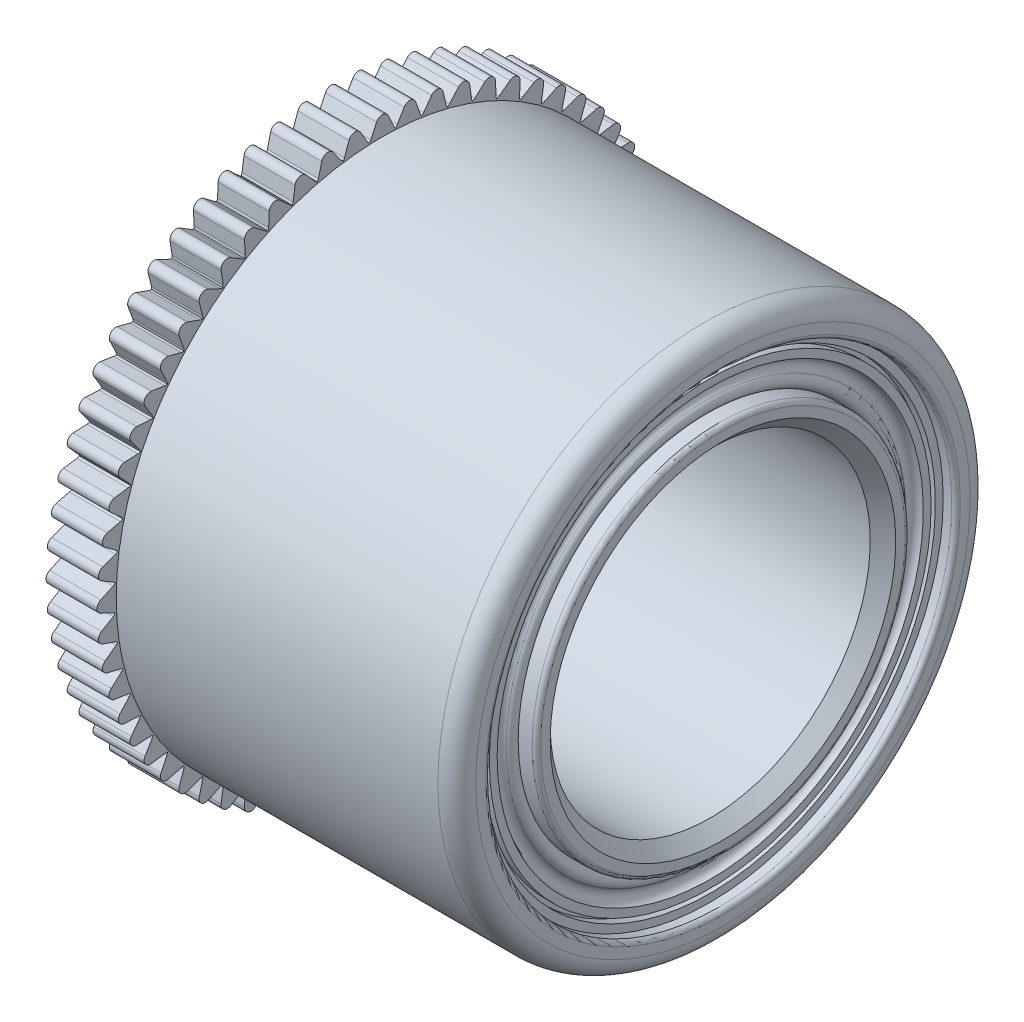
SolidWorks part; units mm, degrees
material "Plain Carbon Steel"
ref_plane "Front Plane" through (0, 0, 0) normal (0, 0, 1) x (1, 0, 0)
ref_plane "Top Plane" through (0, 0, 0) normal (0, 1, 0) x (1, 0, 0)
ref_plane "Right Plane" through (0, 0, 0) normal (1, 0, 0) x (0, 0, -1)
sketch "Sketch1" plane through (0, 0, 0) normal (0, 0, 1) x (1, 0, 0)
  line L0 (-5.842, 0) -> (5.842, 0) construction
  line L1 (-5.842, 4.7727) -> (5.842, 4.7727)
  line L2 (5.842, 4.7727) -> (5.842, 7.9375)
  line L3 (5.842, 7.9375) -> (-4.318, 7.9375)
  line L4 (-4.318, 7.9375) -> (-4.318, 8.509)
  line L5 (-4.318, 8.509) -> (-5.842, 8.509)
  line L6 (-5.842, 8.509) -> (-5.842, 4.7727)
  line L7 (-5.842, -8.509) -> (-4.318, -8.509) construction
  dimension "ID" = 9.5453
  dimension "OD" = 15.875
  dimension "Width" = 11.684
  dimension "Spline OD" = 17.018
  dimension "pt" = 1.524
  dimension "D1" = 3.1648
  dimension "D2" = 17.018
sketch "Sketch2" plane through (0, 0, 0) normal (0, 0, 1) x (1, 0, 0)
  line L0 (5.842, 7.9375) -> (-4.318, 7.9375) construction
  line L1 (5.842, 4.7727) -> (5.842, 5.5639)
  line L2 (5.842, 4.7727) -> (5.842, 7.9375) construction
  line L3 (-5.842, 4.7727) -> (-5.842, 5.5639)
  line L4 (5.842, 7.3728) -> (5.842, 6.9493)
  line L5 (5.842, 6.9493) -> (5.461, 6.9493)
  line L6 (5.461, 6.9493) -> (5.461, 6.7157)
  line L7 (5.461, 6.7157) -> (5.207, 6.7157)
  line L8 (5.207, 6.7157) -> (5.207, 6.5887)
  line L9 (5.207, 6.5887) -> (5.461, 6.5887)
  line L10 (5.461, 6.3551) -> (5.461, 5.5639) construction
  line L11 (5.461, 6.3551) -> (5.207, 6.3551) construction
  line L12 (-5.842, 7.9375) -> (5.2773, 7.9375)
  line L13 (5.842, 5.5639) -> (5.207, 5.5639)
  line L14 (-5.842, 0) -> (5.842, 0) construction
  line L15 (5.461, 6.5887) -> (5.461, 6.3551)
  line L16 (-5.842, 4.7727) -> (5.842, 4.7727)
  line L17 (-5.842, 5.5639) -> (-5.461, 5.5639)
  line L18 (-5.461, 5.5639) -> (-5.461, 6.3551)
  line L19 (-5.461, 6.3551) -> (-5.842, 6.3551)
  line L20 (-5.842, 6.3551) -> (-5.842, 7.9375)
  line L21 (-5.842, 8.509) -> (-5.842, 4.7727) construction
  arc A0 (5.461, 6.3551) -> (5.334, 5.9595) centre (5.461, 6.1369) ccw
  arc A1 (5.2773, 7.9375) -> (5.842, 7.3728) centre (5.2773, 7.3728) cw
  arc A2 (5.334, 5.9595) -> (5.207, 5.5639) centre (5.207, 5.7821) cw
  dimension "D2" = 0.5647
  dimension "D3" = 0.9882
  dimension "D5" = 0.127
  dimension "D6" = 0.254
  dimension "D7" = 1.5824
  dimension "D8" = 0.381
  dimension "D9" = 0.381
  dimension "D1" = 0.7912
revolve "Revolve1" add sketch "Sketch2" angle 360 about L14
chamfer "Chamfer1" distance 0.381 angle 45 2 edges at (-5.842, 0, 4.7727) (5.842, 0, 4.7727)
sketch "Sketch4" plane through (-5.842, 0, 0) normal (-1, 0, 0) x (0, 0, 1)
  circle A1 centre (0, 0) radius 6.3551 construction
  circle A2 centre (0, 0) radius 7.4295
  circle A3 centre (0, 0) radius 7.4295
  circle A4 centre (0, 0) radius 6.3551
  dimension "D1" = 0.508
extrude "Cut-Extrude1" cut sketch "Sketch4" against normal blind 0.127
fillet "Fillet1" radius 0.127 4 edges at (5.842, 0, 5.5639) (5.842, 0, 6.9493) (-5.842, 0, 5.5639) (-5.715, 0, 6.3551)
sketch "Sketch3" plane through (-5.842, 0, 0) normal (1, 0, 0) x (0, 0, -1)
  line L0 (0.1727, 8.399) -> (0.3442, 8.031)
  line L1 (-0.1727, 8.399) -> (-0.3442, 8.031)
  line L2 (0, 8.509) -> (0, 4.7727) construction
  line L3 (-0.3924, 7.9278) -> (0, 0) construction
  line L4 (0, 0) -> (0.3924, 7.9278) construction
  line L5 (0, 8.509) -> (0, 7.9375) construction
  line L6 (0, 7.9375) -> (0, 8.509) construction
  line L7 (0, 4.7727) -> (0, 7.9375) construction
  line L8 (0.3924, 7.9278) -> (0.3943, 7.9658)
  line L9 (-0.3924, 7.9278) -> (-0.3943, 7.9658)
  line L10 (0.3924, 7.9278) -> (0.3442, 8.031) construction
  line L11 (-0.3924, 7.9278) -> (-0.3442, 8.031) construction
  arc A0 (-0.1727, 8.399) -> (0.1727, 8.399) centre (0, 8.3185) cw
  circle A2 centre (0, 0) radius 7.9375 construction
  arc A3 (0.3924, 7.9278) -> (-0.3924, 7.9278) centre (0, 0) ccw
  circle A4 centre (0, 0) radius 7.9375 construction
  arc A5 (0.3442, 8.031) -> (0.3943, 7.9658) centre (0.5169, 8.1115) ccw
  arc A6 (-0.3442, 8.031) -> (-0.3943, 7.9658) centre (-0.5169, 8.1115) cw
  dimension "D1" = 0.1905
  dimension "D2" = 50
  dimension "D3" = 5.667
  dimension "D4" = 0.5715
extrude "Boss-Extrude1" add sketch "Sketch3" along normal up to vertex (1.524 mm away) up to point (-4.318, 8.509, 0)
pattern_circular "CirPattern1" count 64 over 360 of "Boss-Extrude1"
sketch "Sketch5" plane through (0, 0, 0) normal (1, 0, 0) x (0, 0, -1)
  circle A0 centre (0, 0) radius 8.509
equation "\"D2@Sketch2\"=\"D3@Sketch2\"/1.750"
equation "\"D3@Sketch2\"=\"D1@Sketch2\" * 1.25"
equation "\"D7@Sketch2\"=\"D1@Sketch1\"/ 2"
equation "\"D1@Sketch2\"=\"D1@Sketch1\"/4"
equation "\"D1@Sketch3\"=\"D4@Sketch3\"/3"
equation "\"D1@CirPattern1\"=(360/\"D3@Sketch3\")"
equation "\"D2@Sketch1\"=\"Spline OD@Sketch1\""
